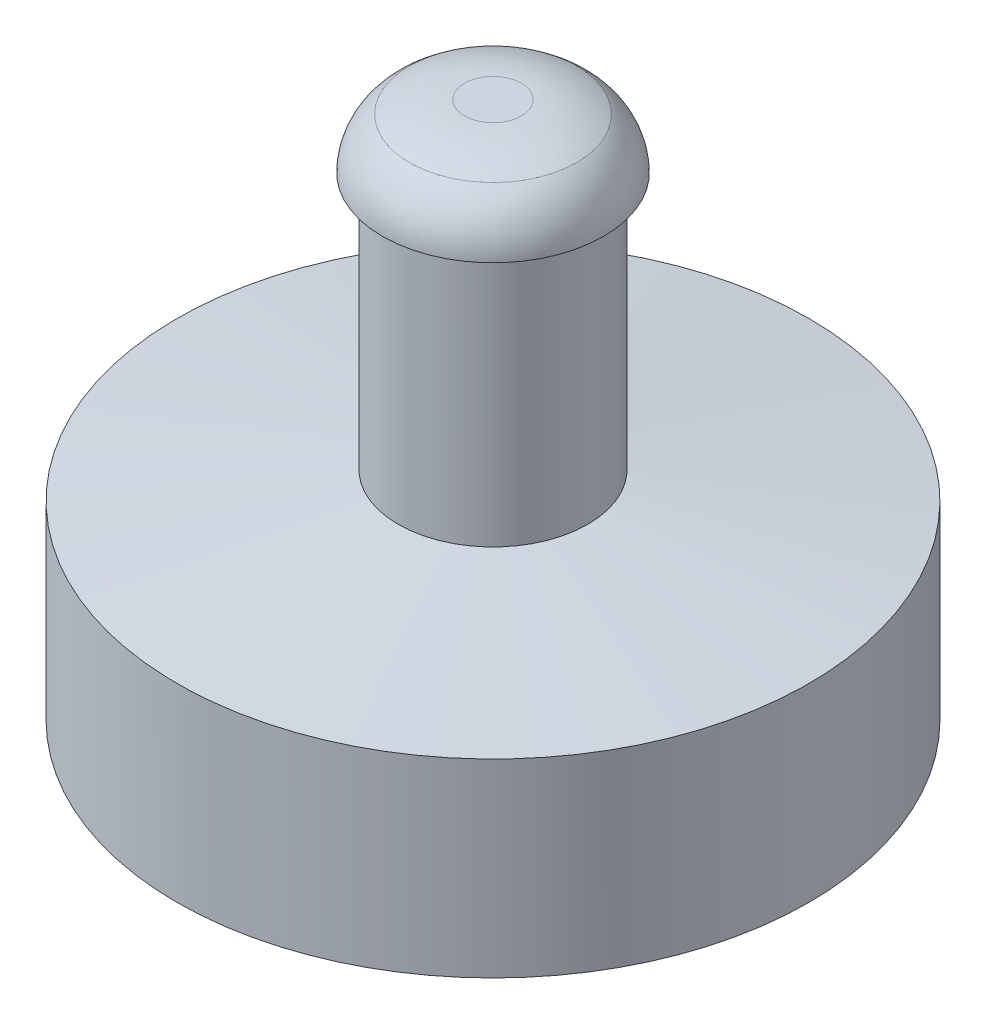
SolidWorks part; units mm, degrees
material "AISI 1020"
ref_plane "Plano frontal" through (0, 0, 0) normal (0, 0, 1) x (1, 0, 0)
ref_plane "Plano superior" through (0, 0, 0) normal (0, 1, 0) x (1, 0, 0)
ref_plane "Plano direito" through (0, 0, 0) normal (1, 0, 0) x (0, 0, -1)
sketch "Esboço2" plane through (0, 0, 0) normal (0, 1, 0) x (1, 0, 0)
  circle A0 centre (0, 0) radius 5
  dimension "D1" = 10
extrude "Ressalto-extrusão2" add sketch "Esboço2" along normal blind 3.5
chamfer "Chanfro1" distance 0.5 angle 83 1 edges at (0, 3.5, 5) first distance on face at (0, 3.5, 5)
sketch "Esboço3" plane through (0, 3.5, 0) normal (0, 1, 0) x (1, 0, 0)
  circle A0 centre (0, 0) radius 1.5
  dimension "D1" = 3
extrude "Ressalto-extrusão3" add sketch "Esboço3" along normal blind 4 and the other way blind 1
sketch "Esboço4" plane through (0, 7.5, 0) normal (0, 1, 0) x (1, 0, 0)
  circle A0 centre (0, 0) radius 1.75
  dimension "D1" = 3.5
extrude "Ressalto-extrusão4" add sketch "Esboço4" along normal blind 1
chamfer "Chanfro2" distance 0.5 angle 55 1 edges at (0, 8.5, 1.75) first distance on face at (0, 8.5, 1.75)
fillet "Filete2" radius 1 1 edges at (0, 8, 1.75)
fillet "Filete3" radius 2 1 edges at (0, 8.5, 1.0359)
